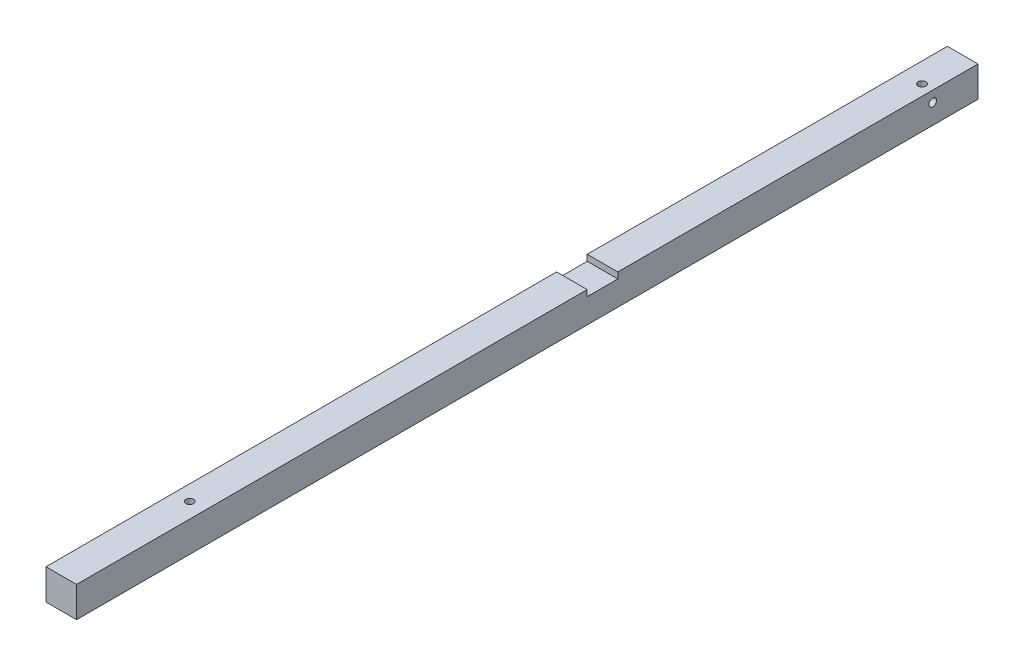
SolidWorks part; units mm, degrees
ref_plane "Plan de face" through (0, 0, 0) normal (0, 0, 1) x (1, 0, 0)
ref_plane "Plan de dessus" through (0, 0, 0) normal (0, 1, 0) x (1, 0, 0)
ref_plane "Plan de droite" through (0, 0, 0) normal (1, 0, 0) x (0, 0, -1)
sketch "Esquisse1" plane through (0, 0, 0) normal (0, 0, 1) x (1, 0, 0)
  line L0 (-5, 5) -> (5, -5) construction
  line L1 (-5, 5) -> (5, 5)
  line L2 (-5, 5) -> (-5, -5)
  line L3 (-5, -5) -> (5, -5)
  line L4 (5, 5) -> (5, -5)
  dimension "D1" = 10
extrude "Boss.-Extru.1" add sketch "Esquisse1" along normal offset from surface (294.8 mm away) 2 offset beyond the face yes
hole_wizard "Trou taraudé M3x0.51" positions "Esquisse3" profile "Esquisse2" tap size "M3x0.5" standard "Ansi Metric"
sketch "Esquisse3" plane through (0, 0, 0) normal (0, 0, -1) x (-1, 0, 0)
  point P0 (0, 0)
sketch "Esquisse2" plane through (0, 0, 0) normal (1, 0, 0) x (0, 1, 0)
  line L0 (0, 0) -> (0, 9.2511)
  line L1 (0, 9.2511) -> (1.25, 8.5)
  line L2 (1.25, 8.5) -> (1.25, 0.275)
  line L3 (1.25, 0.275) -> (1.525, 0)
  line L5 (1.525, 0) -> (0, 0)
  line L6 (-1.25, 0.275) -> (-1.525, 0) construction
  line L10 (0, 9.2511) -> (-1.25, 8.5) construction
  line L11 (0, -6.35) -> (0, 107.95) construction
  dimension "Diamètre du trou pour taraudage" = 2.5
  dimension "Profondeur du trou pour taraudage" = 8.5
  dimension "Diamètre du fraisage entrant" = 3.05
  dimension "Angle du fraisage entrant" = 90
  dimension "Angle de pointe" = 118
cosmetic thread "Filetage de perçage1" parameters "D1"=6, "D2"=3
sketch "Esquisse4" plane through (-5, 0, 0) normal (-1, 0, 0) x (0, 0, 1)
  line L0 (127.8, 3) -> (127.8, 239) construction
  line L1 (127.8, 3) -> (117.8, 3)
  line L2 (127.8, 3) -> (127.8, 5)
  line L3 (127.8, 5) -> (117.8, 5)
  line L4 (117.8, 3) -> (117.8, 5)
  line L5 (117.8, 3) -> (117.8, 239) construction
  line L6 (294.8, 5) -> (0, 5) construction
  dimension "D1" = 2
extrude "Enlèv. mat.-Extru.1" cut sketch "Esquisse4" against normal through all
sketch "Esquisse5" [suppressed] plane through (0, 5, 0) normal (0, 1, 0) x (1, 0, 0)
  line L0 (5, -294.8) -> (5, -127.8) construction
  line L1 (-5, 0) -> (5, 0)
  line L2 (-5, 0) -> (-5, -53.6)
  line L3 (-5, -53.6) -> (5, -53.6)
  line L4 (5, 0) -> (5, -53.6)
  line L5 (5, -117.8) -> (5, 0) construction
  line L6 (5, -53.6) -> (-5, -53.6) construction
hole_wizard "Trou taraudé M3x0.52" positions "Esquisse8" profile "Esquisse7" tap size "M3x0.5" standard "Ansi Metric" end condition through all
sketch "Esquisse8" plane through (0, -5, 0) normal (0, -1, 0) x (-1, 0, 0)
  point P0 (-1.5, -14.8)
sketch "Esquisse7" plane through (1.5, -5, 14.8) normal (1, 0, 0) x (0, 0, -1)
  line L0 (0, 0) -> (0, 10)
  line L1 (0, 10) -> (1.25, 10)
  line L2 (1.25, 10) -> (1.25, 0.275)
  line L3 (1.25, 0.275) -> (1.525, 0)
  line L5 (1.525, 0) -> (0, 0)
  line L6 (-1.25, 0.275) -> (-1.525, 0) construction
  line L11 (0, -6.35) -> (0, 107.95) construction
  dimension "Diamètre du trou pour taraudage jusqu'au prochain" = 2.5
  dimension "Profondeur du trou pour taraudage jusqu'au prochain" = 10
  dimension "Diamètre du fraisage entrant" = 3.05
  dimension "Angle du fraisage entrant" = 90
cosmetic thread "Filetage de perçage2" parameters "D2"=3
hole_wizard "Trou taraudé M3x0.53" positions "Esquisse10" profile "Esquisse9" tap size "M3x0.5" standard "Ansi Metric" end condition through all
sketch "Esquisse10" plane through (-5, 0, 0) normal (-1, 0, 0) x (0, 0, 1)
  point P0 (14.8, 1.5)
sketch "Esquisse9" plane through (-5, 1.5, 14.8) normal (0, 1, 0) x (0, 0, 1)
  line L0 (0, 0) -> (0, 10)
  line L1 (0, 10) -> (1.25, 10)
  line L2 (1.25, 10) -> (1.25, 0.275)
  line L3 (1.25, 0.275) -> (1.525, 0)
  line L5 (1.525, 0) -> (0, 0)
  line L6 (-1.25, 0.275) -> (-1.525, 0) construction
  line L11 (0, -6.35) -> (0, 107.95) construction
  dimension "Diamètre du trou pour taraudage jusqu'au prochain" = 2.5
  dimension "Profondeur du trou pour taraudage jusqu'au prochain" = 10
  dimension "Diamètre du fraisage entrant" = 3.05
  dimension "Angle du fraisage entrant" = 90
cosmetic thread "Filetage de perçage3" parameters "D2"=3
extrude "Enlèv. mat.-Extru.2" [suppressed] cut sketch "Esquisse5" against normal through all
hole_wizard "Trou taraudé M3x0.54" positions "Esquisse12" profile "Esquisse11" tap size "M3x0.5" standard "Ansi Metric" end condition through all
sketch "Esquisse12" plane through (0, -5, 0) normal (0, -1, 0) x (-1, 0, 0)
  point P0 (0, -252.8)
sketch "Esquisse11" plane through (0, -5, 252.8) normal (1, 0, 0) x (0, 0, -1)
  line L0 (0, 0) -> (0, 10)
  line L1 (0, 10) -> (1.25, 10)
  line L2 (1.25, 10) -> (1.25, 0.275)
  line L3 (1.25, 0.275) -> (1.525, 0)
  line L5 (1.525, 0) -> (0, 0)
  line L6 (-1.25, 0.275) -> (-1.525, 0) construction
  line L11 (0, -6.35) -> (0, 107.95) construction
  dimension "Diamètre du trou pour taraudage jusqu'au prochain" = 2.5
  dimension "Profondeur du trou pour taraudage jusqu'au prochain" = 10
  dimension "Diamètre du fraisage entrant" = 3.05
  dimension "Angle du fraisage entrant" = 90
cosmetic thread "Filetage de perçage5" parameters "D1"=10, "D2"=3
